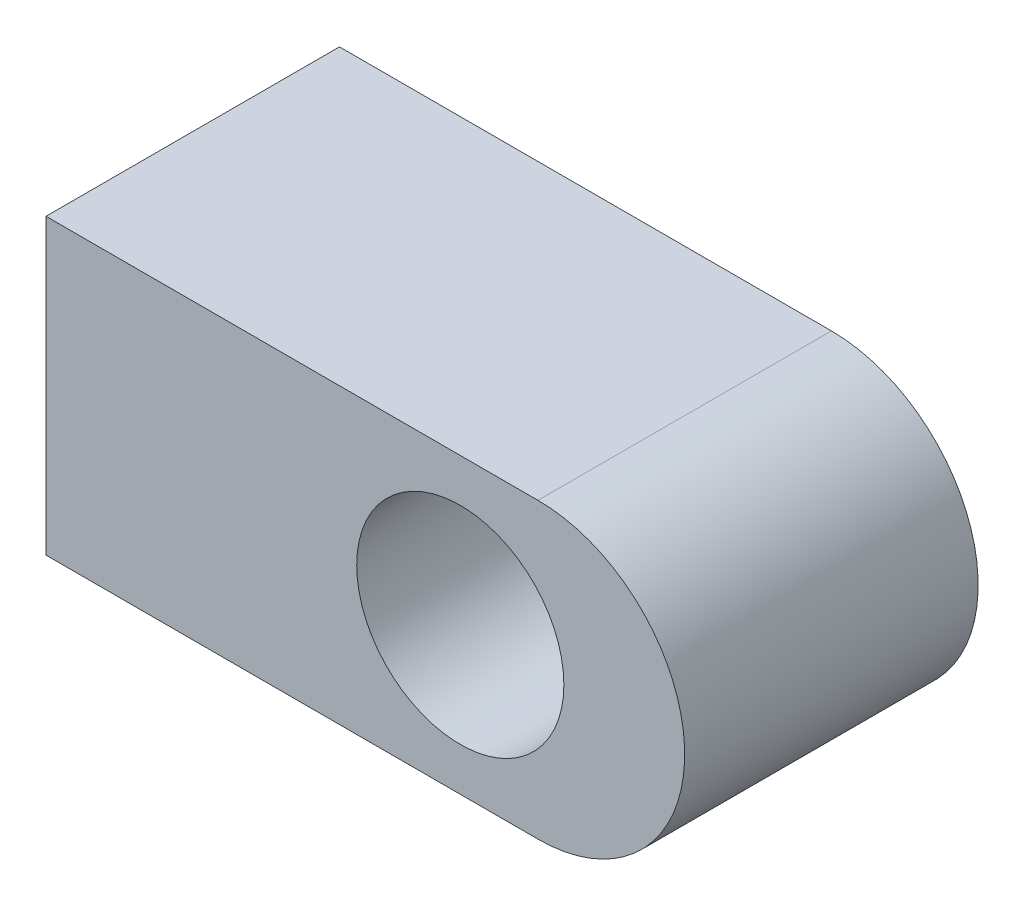
SolidWorks part; units mm, degrees
ref_plane "Płaszczyzna przednia" through (0, 0, 0) normal (0, 0, 1) x (1, 0, 0)
ref_plane "Płaszczyzna górna" through (0, 0, 0) normal (0, 1, 0) x (1, 0, 0)
ref_plane "Płaszczyzna prawa" through (0, 0, 0) normal (1, 0, 0) x (0, 0, -1)
sketch "Szkic1" plane through (0, 0, 0) normal (0, 0, 1) x (1, 0, 0)
  line L2 (-43.0292, 27.5155) -> (-43.0292, -6.4845)
  line L9 (-43.0292, -6.4845) -> (4.9708, -6.4845)
  line L10 (-43.0292, -6.4845) -> (-43.0292, 27.5155)
  line L11 (-43.0292, 27.5155) -> (4.9708, 27.5155)
  line L13 (-43.0292, -6.4845) -> (4.9708, 27.5155) construction
  line L14 (-43.0292, 27.5155) -> (4.9708, -6.4845) construction
  line L15 (4.9708, -6.4845) -> (13.9708, -6.4845)
  line L16 (4.9708, 27.5155) -> (13.9708, 27.5155)
  circle A5 centre (4.9708, 10.5155) radius 12
  arc A7 (30.9708, 10.5155) -> (13.9708, -6.4845) centre (13.9708, 10.5155) cw
  arc A8 (30.9708, 10.5155) -> (13.9708, 27.5155) centre (13.9708, 10.5155) ccw
  point P0 (-49.0292, 10.5155)
  point P1 (0, 0)
  point P7 (-19.0292, 10.5155)
  point P9 (-43.0292, 10.5155)
  point P14 (0, 0)
  point P17 (0, 0)
  point P19 (0, 0)
  point P21 (0, 0)
  dimension "D3" = 34
  dimension "D4" = 48
extrude "Dodanie-wyciągnięcie6" add sketch "Szkic1" along normal blind 17 and the other way blind 17 contours A7 A8 L16 L11 L2 L9 L15 A5 region at (-10.7182, 10.5155, 0)
